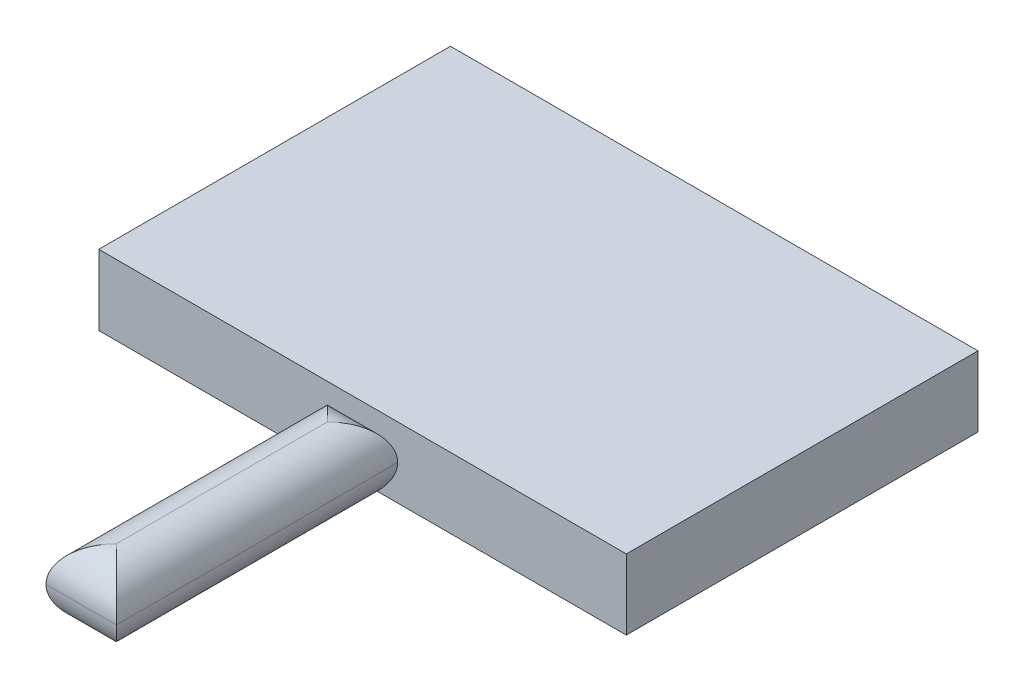
SolidWorks part; units mm, degrees
ref_plane "Front Plane" through (0, 0, 0) normal (0, 0, 1) x (1, 0, 0)
ref_plane "Top Plane" through (0, 0, 0) normal (0, 1, 0) x (1, 0, 0)
ref_plane "Right Plane" through (0, 0, 0) normal (1, 0, 0) x (0, 0, -1)
sketch "Sketch1" plane through (0, 0, 0) normal (0, 1, 0) x (1, 0, 0)
  line L0 (7.5, 10) -> (7.5, 0) construction
  line L1 (0, 0) -> (15, 0)
  line L2 (0, 0) -> (0, 10)
  line L3 (0, 10) -> (15, 10)
  line L4 (15, 0) -> (15, 10)
  line L5 (6.5, 0) -> (6.5, -8)
  line L6 (6.5, -8) -> (8.5, -8)
  line L7 (8.5, -8) -> (8.5, 0)
  line L8 (7.5, -8) -> (7.5, 0) construction
  dimension "D1" = 15
  dimension "D2" = 10
  dimension "D3" = 2
  dimension "D4" = 8
extrude "Boss-Extrude1" add sketch "Sketch1" along normal blind 2 contours L1 L4 L3 L2 region at (7.5, 0, -5)
extrude "Boss-Extrude2" add sketch "Sketch1<3>" along normal blind 2 contours L6 L7 L1 L5 region at (7.5, 0, 4)
sketch "Sketch1<3>" plane through (0, 0, 0) normal (0, 1, 0) x (1, 0, 0) same geometry as "Sketch1"
split "Split1" bodies to split 102 resulting bodies 103 104 split by face at (3.25, 1, 0)
fillet "Fillet1" radius 1 8 edges at (7.5, 0, 8) (8.5, 0, 4) (6.5, 0, 4) (7.5, 2, 8) (8.5, 2, 4) (6.5, 2, 4) (7.5, 0, 0) (7.5, 2, 0)
